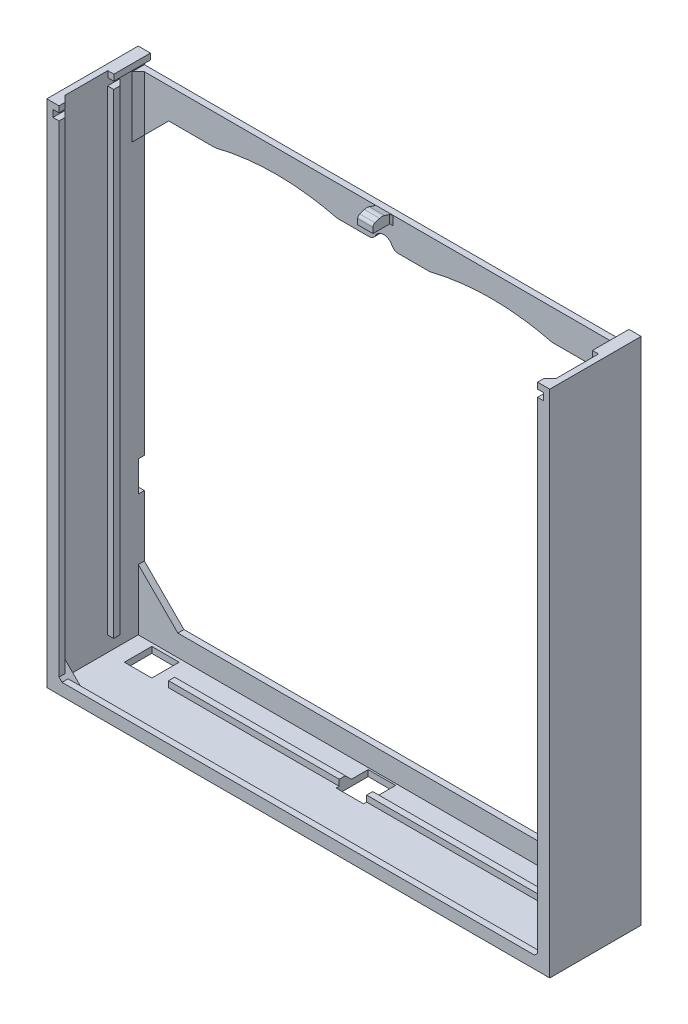
SolidWorks part; units mm, degrees
ref_plane "Front Plane" through (0, 0, 0) normal (0, 0, 1) x (1, 0, 0)
ref_plane "Top Plane" through (0, 0, 0) normal (0, 1, 0) x (1, 0, 0)
ref_plane "Right Plane" through (0, 0, 0) normal (1, 0, 0) x (0, 0, -1)
sketch "Sketch1" plane through (0, 0, 0) normal (0, 0, 1) x (1, 0, 0)
  line L0 (-102.235, 102.235) -> (-104.775, 102.235)
  line L1 (102.235, -102.235) -> (-102.235, -102.235)
  line L2 (102.235, -102.235) -> (102.235, 102.235)
  line L3 (102.235, 102.235) -> (-102.235, 102.235) construction
  line L4 (-102.235, -102.235) -> (-102.235, 102.235)
  line L5 (102.235, -102.235) -> (-102.235, 102.235) construction
  line L6 (102.235, 102.235) -> (-102.235, -102.235) construction
  line L7 (-104.775, 102.235) -> (-104.775, -104.775)
  line L8 (-104.775, -104.775) -> (104.775, -104.775)
  line L9 (104.775, -104.775) -> (104.775, 102.235)
  line L10 (104.775, 102.235) -> (102.235, 102.235)
  point P0 (0, 0)
  dimension "D1" = 204.47
  dimension "D3" = 2.54
  dimension "D4" = 2.54
extrude "Boss-Extrude1" add sketch "Sketch1" along normal blind 35.56
sketch "Sketch2" plane through (0, 0, 35.56) normal (0, 0, 1) x (1, 0, 0)
  line L0 (-102.235, -102.235) -> (-102.235, -95.885)
  line L1 (-102.235, -102.235) -> (-102.235, 102.235) construction
  line L2 (-102.235, -95.885) -> (-95.885, -102.235)
  line L3 (102.235, -102.235) -> (-102.235, -102.235) construction
  line L4 (-95.885, -102.235) -> (-102.235, -102.235)
  line L5 (102.235, -102.235) -> (102.235, -95.885)
  line L6 (102.235, 102.235) -> (102.235, -102.235) construction
  line L7 (102.235, -95.885) -> (95.885, -102.235)
  line L8 (102.235, -102.235) -> (95.885, -102.235)
  dimension "D1" = 6.35
extrude "Boss-Extrude2" add sketch "Sketch2" against normal blind 2.54
sketch "Sketch4" plane through (0, 102.235, 0) normal (0, 1, 0) x (1, 0, 0)
  line L0 (-102.235, -33.02) -> (-99.695, -35.56)
  line L1 (-95.885, -35.56) -> (-102.235, -35.56) construction
  line L2 (-99.695, -35.56) -> (-102.235, -35.56)
  line L3 (-102.235, -35.56) -> (-102.235, -33.02)
  line L4 (102.235, -33.02) -> (99.695, -35.56)
  line L5 (102.235, -35.56) -> (95.885, -35.56) construction
  line L6 (99.695, -35.56) -> (102.235, -35.56)
  line L7 (102.235, -35.56) -> (102.235, -33.02)
  dimension "D1" = 2.54
extrude "Boss-Extrude3" add sketch "Sketch4" against normal up to surface (204.47 mm away) up to face at (0, -102.235, 25.4)
sketch "Sketch5" plane through (-102.235, 0, 0) normal (1, 0, 0) x (0, 0, -1)
  line L0 (-33.02, -102.235) -> (-35.56, -102.235)
  line L3 (-35.56, -102.235) -> (-35.56, -99.695)
  line L4 (-35.56, -99.695) -> (-33.02, -102.235)
  dimension "D1" = 2.54
extrude "Boss-Extrude4" add sketch "Sketch5" along normal up to surface (204.47 mm away) up to face at (102.235, -19.177, 19.812)
sketch "Sketch6" plane through (0, -102.235, 0) normal (0, 1, 0) x (1, 0, 0)
  line L0 (0, -33.02) -> (0, -29.845) construction
  line L1 (95.885, -33.02) -> (-95.885, -33.02) construction
  line L2 (0, -29.845) -> (0, -17.145) construction
  line L3 (0, -17.145) -> (0, -15.9512) construction
  line L4 (0, -15.9512) -> (0, -15.3162) construction
  line L5 (0, -15.3162) -> (-102.235, -15.3162)
  line L6 (-102.235, -33.02) -> (-102.235, 0) construction
  line L7 (-102.235, -15.3162) -> (-102.235, -12.7762)
  line L8 (-102.235, -12.7762) -> (102.235, -12.7762)
  line L9 (102.235, -15.3162) -> (102.235, -12.7762)
  line L10 (0, -15.3162) -> (102.235, -15.3162)
  point P15 (0, -12.7762)
  dimension "D1" = 1.1938
  dimension "D2" = 3.175
  dimension "D3" = 12.7
  dimension "D4" = 0.635
  dimension "D5" = 2.54
extrude "Boss-Extrude5" add sketch "Sketch6" along normal blind 2.54
sketch "Sketch7" plane through (-102.235, 0, 0) normal (1, 0, 0) x (0, 0, -1)
  line L0 (-12.7762, -99.695) -> (-10.2362, -102.235)
  line L1 (-12.7762, -102.235) -> (0, -102.235) construction
  line L2 (-10.2362, -102.235) -> (-12.7762, -102.235)
  line L3 (-12.7762, -102.235) -> (-12.7762, -99.695)
extrude "Boss-Extrude6" add sketch "Sketch7" along normal up to surface (204.47 mm away) up to face at (102.235, -55.5272, 17.2494)
sketch "Sketch8" plane through (0, 102.235, 0) normal (0, 1, 0) x (1, 0, 0)
  line L0 (-102.235, -15.3162) -> (-99.695, -15.3162)
  line L1 (-102.235, -15.3162) -> (102.235, -15.3162) construction
  line L2 (-99.695, -15.3162) -> (-99.695, -12.7762)
  line L3 (102.235, -12.7762) -> (-102.235, -12.7762) construction
  line L4 (-99.695, -12.7762) -> (-102.235, -10.2362)
  line L5 (-102.235, -10.2362) -> (-102.235, -15.3162)
  line L6 (0, 0) -> (0, -61.9382) construction
  line L7 (102.235, 0) -> (-102.235, 0) construction
  line L8 (99.695, -15.3162) -> (99.695, -12.7762)
  line L9 (99.695, -12.7762) -> (102.235, -10.2362)
  line L10 (102.235, -10.2362) -> (102.235, -15.3162)
  line L11 (102.235, -15.3162) -> (99.695, -15.3162)
  dimension "D1" = 2.54
extrude "Boss-Extrude7" add sketch "Sketch8" against normal up to surface (204.47 mm away) up to face at (0, -102.235, 27.1187)
sketch "Sketch9" plane through (0, 0, 35.56) normal (0, 0, 1) x (1, 0, 0)
  line L0 (-104.775, 102.235) -> (-99.695, 102.235)
  line L1 (-99.695, 102.235) -> (-99.695, -98.425)
  line L2 (-99.695, -98.425) -> (-98.425, -99.695)
  line L3 (-98.425, -99.695) -> (98.425, -99.695)
  line L4 (98.425, -99.695) -> (99.695, -98.425)
  line L5 (99.695, -98.425) -> (99.695, 102.235)
  line L6 (99.695, 102.235) -> (104.775, 102.235)
  line L7 (104.775, 102.235) -> (104.775, -104.775)
  line L8 (104.775, -104.775) -> (-104.775, -104.775)
  line L9 (-104.775, 102.235) -> (-104.775, -104.775)
extrude "Boss-Extrude8" add sketch "Sketch9" along normal blind 2.54
sketch "Sketch10" plane through (0, 0, 0) normal (0, 0, -1) x (-1, 0, 0)
  line L0 (-102.235, 102.235) -> (102.235, 102.235)
  line L1 (102.235, 102.235) -> (102.235, 89.535)
  line L2 (102.235, -102.235) -> (102.235, 102.235) construction
  line L3 (102.235, 89.535) -> (-102.235, 89.535) construction
  line L4 (-102.235, -102.235) -> (-102.235, 102.235) construction
  line L5 (-102.235, 89.535) -> (-102.235, 102.235)
  line L6 (-102.235, 89.535) -> (-102.235, 76.835)
  line L7 (-102.235, 102.235) -> (-102.235, -102.235) construction
  line L8 (-102.235, 76.835) -> (-89.535, 89.535)
  line L9 (-89.535, 89.535) -> (89.535, 89.535)
  line L10 (89.535, 89.535) -> (102.235, 76.835)
  line L11 (102.235, 89.535) -> (102.235, 76.835)
  line L12 (-102.235, -102.235) -> (-76.835, -102.235)
  line L13 (-102.235, -102.235) -> (102.235, -102.235) construction
  line L14 (-76.835, -102.235) -> (-102.235, -76.835)
  line L15 (-102.235, -76.835) -> (-102.235, -102.235)
  line L16 (102.235, -102.235) -> (76.835, -102.235)
  line L17 (76.835, -102.235) -> (102.235, -76.835)
  line L18 (102.235, -102.235) -> (102.235, 102.235) construction
  line L19 (102.235, -76.835) -> (102.235, -102.235)
  dimension "D1" = 12.7
  dimension "D2" = 45
  dimension "D3" = 45
  dimension "D4" = 25.4
extrude "Boss-Extrude9" add sketch "Sketch10" against normal blind 2.54
sketch "Sketch11" plane through (0, 0, 0) normal (0, 0, -1) x (-1, 0, 0)
  line L0 (0, 89.535) -> (0, 51.4026) construction
  line L1 (-89.535, 89.535) -> (89.535, 89.535) construction
  line L2 (-89.535, 89.535) -> (0, 89.535) construction
  line L3 (0, 89.535) -> (-44.7675, 95.885) construction
  line L4 (-44.7675, 95.885) -> (-89.535, 89.535) construction
  line L5 (-44.7675, 95.885) -> (-44.7675, 89.535) construction
  line L6 (-44.7675, 89.535) -> (-19.3675, 89.535)
  line L7 (-44.7675, 89.535) -> (-70.1675, 89.535)
  line L8 (-19.3675, 89.535) -> (-44.7675, 95.885) construction
  line L9 (-44.7675, 95.885) -> (-70.1675, 89.535) construction
  line L10 (44.7675, 89.535) -> (19.3675, 89.535)
  line L11 (19.3675, 89.535) -> (44.7675, 95.885) construction
  line L12 (44.7675, 95.885) -> (70.1675, 89.535) construction
  line L13 (44.7675, 89.535) -> (70.1675, 89.535)
  circle A0 centre (0, 89.535) radius 3.81
  spline S0 degree 2 poles (-19.3675, 89.535) (-44.7675, 95.885) (-70.1675, 89.535) knots 0 0 0 1 1 1
  spline S1 degree 2 poles (19.3675, 89.535) (44.7675, 95.885) (70.1675, 89.535) knots 0 0 0 1 1 1
  dimension "D1" = 7.62
  dimension "D2" = 25.4
  dimension "D3" = 25.4
  dimension "D4" = 6.35
extrude "Cut-Extrude1" cut sketch "Sketch11" against normal blind 2.54
fillet "Fillet1" radius 3.175 6 edges at (-70.1675, 89.535, 1.27) (70.1675, 89.535, 1.27) (19.3675, 89.535, 1.27) (-19.3675, 89.535, 1.27) (-3.81, 89.535, 1.27) (3.81, 89.535, 1.27)
chamfer "Chamfer1" distance 2.54 angle 45 2 edges at (102.235, 89.535, 2.54) (-102.235, 89.535, 2.54)
sketch "Sketch12" plane through (0, 102.235, 0) normal (0, 1, 0) x (1, 0, 0)
  line L0 (-99.695, -38.1) -> (-104.775, -38.1) construction
  line L1 (-104.775, 0) -> (-102.235, 0)
  line L2 (-104.775, 0) -> (-104.775, -38.1)
  line L3 (-104.775, -38.1) -> (-102.235, -38.1)
  line L4 (-102.235, 0) -> (-102.235, -38.1)
  line L5 (104.775, -38.1) -> (99.695, -38.1) construction
  line L6 (104.775, 0) -> (102.235, 0)
  line L7 (104.775, 0) -> (104.775, -38.1)
  line L8 (104.775, -38.1) -> (102.235, -38.1)
  line L9 (102.235, 0) -> (102.235, -38.1)
  dimension "D1" = 2.54
  dimension "D2" = 2.54
extrude "Boss-Extrude10" add sketch "Sketch12" along normal blind 5.461
sketch "Sketch13" plane through (0, 0, 38.1) normal (0, 0, 1) x (1, 0, 0)
  line L0 (0, 102.235) -> (0, 67.16) construction
  line L1 (-102.235, 107.696) -> (-99.695, 107.696)
  line L2 (-102.235, 107.696) -> (-102.235, 105.156)
  line L3 (-102.235, 105.156) -> (-99.695, 105.156)
  line L4 (-99.695, 107.696) -> (-99.695, 105.156)
  line L5 (-99.695, 102.235) -> (99.695, 102.235) construction
  line L6 (102.235, 107.696) -> (102.235, 105.156)
  line L7 (102.235, 107.696) -> (99.695, 107.696)
  line L8 (99.695, 107.696) -> (99.695, 105.156)
  line L9 (102.235, 105.156) -> (99.695, 105.156)
  dimension "D1" = 2.54
  dimension "D2" = 2.54
extrude "Boss-Extrude11" add sketch "Sketch13" against normal up to surface (38.1 mm away) up to face at (-2.5029, 52.7021, 0)
sketch "Sketch14" plane through (0, 0, 0) normal (1, 0, 0) x (0, 0, -1)
  line L0 (-2.54, 102.235) -> (-6.35, 102.235) construction
  line L1 (-5.08, 102.235) -> (0, 102.235) construction
  line L3 (-2.54, 102.235) -> (-2.54, 79.375) construction
  line L5 (-10.16, 99.06) -> (-2.54, 99.06)
  line L6 (-2.54, 99.06) -> (-2.54, 102.235)
  line L7 (-6.35, 99.06) -> (-6.35, 103.505) construction
  line L8 (-6.35, 103.505) -> (-2.54, 102.235)
  line L9 (-10.16, 99.06) -> (-10.16, 102.235)
  line L10 (-6.35, 103.505) -> (-10.16, 102.235)
  dimension "D1" = 3.81
  dimension "D2" = 1.27
  dimension "D3" = 0
  dimension "D4" = 3.175
extrude "Boss-Extrude12" add sketch "Sketch14" along normal blind 3.175 and the other way blind 3.175
fillet "Fillet2" radius 3.175 1 edges at (0, 103.505, 6.35)
chamfer "Chamfer2" distance 0.635 angle 45 3 edges at (-3.175, 100.6475, 2.54) (0, 99.06, 2.54) (3.175, 100.6475, 2.54)
fillet "Fillet3" radius 1.27 1 edges at (0, 102.235, 10.16)
sketch "Sketch15" plane through (0, -102.235, 0) normal (0, 1, 0) x (1, 0, 0)
  line L0 (0, 0) -> (0, -8.636) construction
  line L1 (76.835, 0) -> (-76.835, 0) construction
  line L2 (-89.535, 0) -> (-89.535, -7.6581) construction
  line L3 (-102.235, -15.3162) -> (102.235, -15.3162) construction
  line L4 (-83.82, -15.3162) -> (-95.25, -15.3162)
  line L5 (-83.82, -15.3162) -> (-83.82, 0) construction
  line L6 (-83.82, 0) -> (-95.25, 0) construction
  line L7 (-95.25, -15.3162) -> (-95.25, 0) construction
  line L8 (-83.82, -15.3162) -> (-95.25, 0) construction
  line L9 (-83.82, 0) -> (-95.25, -15.3162) construction
  line L15 (-83.82, -15.3162) -> (-83.82, -3.8862)
  line L16 (-83.82, -3.8862) -> (-95.25, -3.8862)
  line L17 (-95.25, -3.8862) -> (-95.25, -15.3162)
  line L18 (-5.715, -10.2362) -> (-5.715, -15.3162)
  line L19 (-104.775, -38.1) -> (-104.775, 0) construction
  line L20 (0, -8.636) -> (0, -10.2362) construction
  line L21 (102.235, -10.2362) -> (-102.235, -10.2362) construction
  line L23 (5.715, -3.2512) -> (-5.715, -3.2512)
  line L24 (5.715, -3.2512) -> (5.715, -10.2362)
  line L26 (-5.715, -3.2512) -> (-5.715, -10.2362)
  line L27 (5.715, -3.2512) -> (-5.715, -10.2362) construction
  line L28 (5.715, -10.2362) -> (-5.715, -3.2512) construction
  line L29 (5.715, -10.2362) -> (5.715, -15.3162)
  line L31 (5.715, -15.3162) -> (5.715, -16.5862)
  line L32 (5.715, -16.5862) -> (-5.715, -16.5862)
  line L33 (-5.715, -15.3162) -> (-5.715, -16.5862)
  point P17 (0, -6.7437)
  dimension "D1" = 11.43
  dimension "D2" = 1.27
  dimension "D3" = 11.43
  dimension "D4" = 9.525
  dimension "D5" = 11.43
  dimension "D6" = 11.43
  dimension "D7" = 11.43
extrude "Cut-Extrude2" cut sketch "Sketch15" against normal blind 3.175 and the other way blind 46.99
sketch "Sketch16" plane through (0, -102.235, 0) normal (0, 1, 0) x (1, 0, 0)
  line L0 (-89.535, -15.3162) -> (-89.535, -3.8862) construction
  line L1 (-5.715, 9.9172) -> (5.715, 9.9172)
  line L2 (-5.715, 9.9172) -> (-5.715, -27.1892)
  line L3 (-5.715, -27.1892) -> (5.715, -27.1892)
  line L4 (5.715, 9.9172) -> (5.715, -27.1892)
  line L5 (-5.715, 9.9172) -> (5.715, -27.1892) construction
  line L6 (-5.715, -27.1892) -> (5.715, 9.9172) construction
  line L7 (-95.25, -15.3162) -> (-83.82, -15.3162) construction
  line L8 (-83.82, -3.8862) -> (-95.25, -3.8862) construction
  line L9 (-89.535, -9.6012) -> (-99.0769, -9.6012) construction
  line L10 (-102.235, -33.02) -> (-102.235, -15.3162) construction
  line L11 (-76.835, -3.4324) -> (-102.235, -3.4324)
  line L12 (-76.835, -3.4324) -> (-76.835, -15.77)
  line L13 (-76.835, -15.77) -> (-102.235, -15.77)
  line L14 (-102.235, -3.4324) -> (-102.235, -15.77)
  line L15 (-76.835, -3.4324) -> (-102.235, -15.77) construction
  line L16 (-76.835, -15.77) -> (-102.235, -3.4324) construction
  point P0 (0, -8.636)
  dimension "D1" = 11.43
extrude "Cut-Extrude3" cut sketch "Sketch16" along normal blind 6.35
sketch "Sketch17" plane through (0, 107.696, 0) normal (0, 1, 0) x (1, 0, 0)
  line L0 (-102.235, -38.1) -> (-102.235, -33.02) construction
  line L1 (-102.235, -33.02) -> (-99.695, -35.56)
  line L2 (-99.695, -35.56) -> (-99.695, -38.1) construction
  line L3 (-99.695, -38.1) -> (-102.235, -38.1) construction
  line L4 (-99.695, -35.56) -> (-99.695, -15.24)
  line L5 (-99.695, 0) -> (-99.695, -38.1) construction
  line L6 (-99.695, -15.24) -> (-102.235, -15.24)
  line L7 (-102.235, -15.24) -> (-102.235, -33.02)
  line L8 (0, 0) -> (0, -67.9912) construction
  line L9 (102.235, 0) -> (-102.235, 0) construction
  line L10 (99.695, -15.24) -> (102.235, -15.24)
  line L11 (99.695, -35.56) -> (99.695, -15.24)
  line L12 (102.235, -33.02) -> (99.695, -35.56)
  line L13 (102.235, -15.24) -> (102.235, -33.02)
  dimension "D1" = 5.08
  dimension "D2" = 2.54
  dimension "D3" = 2.54
  dimension "D4" = 2.54
  dimension "D5" = 20.32
extrude "Cut-Extrude4" cut sketch "Sketch17" against normal up to surface (2.54 mm away) up to face at (100.965, 105.156, 19.05)
sketch "Sketch18" plane through (-102.235, 0, 0) normal (1, 0, 0) x (0, 0, -1)
  line L0 (0, -76.835) -> (0, 76.835) construction
  line L1 (0, -38.735) -> (-2.54, -38.735)
  line L2 (0, -38.735) -> (0, -51.435)
  line L3 (0, -51.435) -> (-2.54, -51.435)
  line L4 (-2.54, -38.735) -> (-2.54, -51.435)
  line L5 (-33.02, -102.235) -> (-2.54, -102.235) construction
  dimension "D1" = 2.54
  dimension "D2" = 50.8
  dimension "D3" = 12.7
extrude "Cut-Extrude5" cut sketch "Sketch18" against normal blind 25.4
sketch "Sketch19" plane through (0, 0, 2.54) normal (0, 0, 1) x (1, 0, 0)
  line L0 (85.725, -93.345) -> (-85.725, -93.345)
  line L1 (76.835, -102.235) -> (102.235, -76.835) construction
  line L2 (-102.235, -76.835) -> (-76.835, -102.235) construction
  line L3 (-85.725, -93.345) -> (-76.835, -102.235)
  line L4 (-76.835, -102.235) -> (76.835, -102.235)
  line L5 (76.835, -102.235) -> (85.725, -93.345)
  line L6 (-104.775, -104.775) -> (104.775, -104.775) construction
  dimension "D1" = 8.89
extrude "Boss-Extrude13" add sketch "Sketch19" against normal up to surface (2.54 mm away) up to face at (-12.891, 47.7786, 0)
